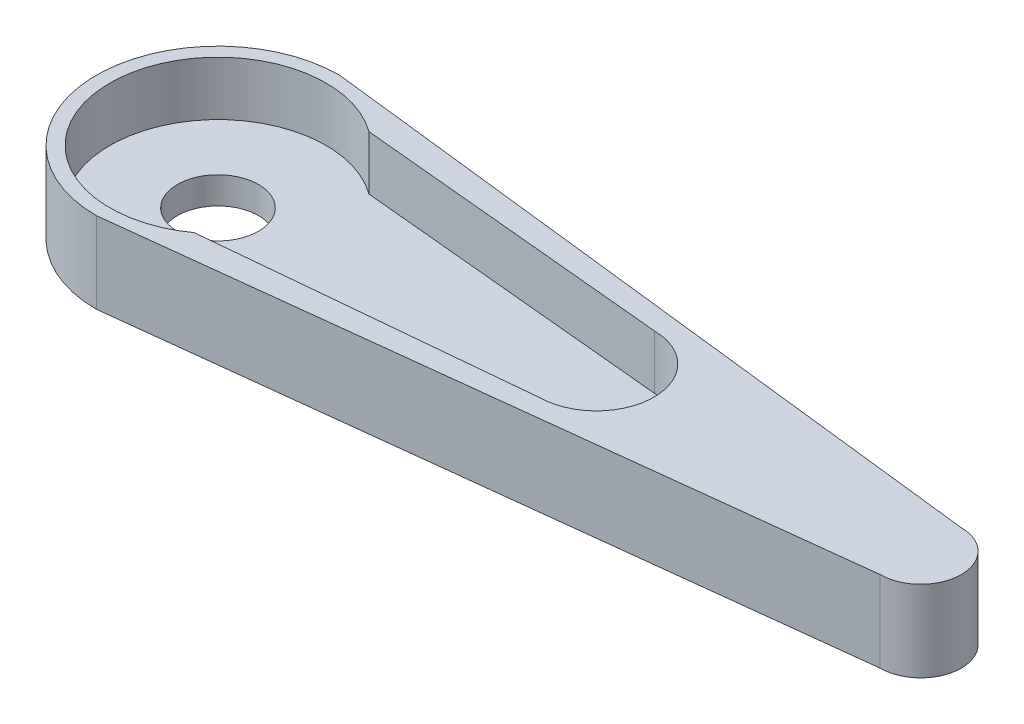
SolidWorks part; units mm, degrees
ref_plane "Front Plane" through (0, 0, 0) normal (0, 0, 1) x (1, 0, 0)
ref_plane "Top Plane" through (0, 0, 0) normal (0, 1, 0) x (1, 0, 0)
ref_plane "Right Plane" through (0, 0, 0) normal (1, 0, 0) x (0, 0, -1)
sketch "Sketch2" plane through (0, 0, 0) normal (0, 1, 0) x (1, 0, 0)
  line L0 (-24.822, 2.75) -> (-24.822, -2.75) construction
  line L1 (-26.9871, 0) -> (-12.9871, 0) construction
  line L4 (-26.9871, 4.5) -> (-12.8647, 2.8705)
  line L5 (-0.9871, -1.5) -> (-26.9871, -4.5)
  line L6 (-26.9871, 0) -> (-1.9871, 0) construction
  line L7 (-26.9871, -4.5) -> (-0.1594, -1.4045) construction
  line L8 (-26.9871, 4.5) -> (-0.9871, 1.5) construction
  line L10 (-12.8647, 2.8705) -> (-0.9871, 1.5)
  line L11 (-24.775, 3.2478) -> (-12.94, 2.1284)
  line L12 (-12.94, -2.1284) -> (-24.775, -3.2478)
  circle A1 centre (-26.9871, 0) radius 1.5
  circle A3 centre (-26.9871, 0) radius 4.5
  circle A4 centre (-12.9871, 0) radius 2.6306
  circle A5 centre (-0.9871, 0) radius 1.5
  circle A6 centre (-12.9871, 0) radius 2.1306
  circle A7 centre (-26.9871, 0) radius 4
  point P1 (-26.9871, 4.5)
  point P5 (-26.9871, -4.5)
  point P8 (-0.9871, -2.9961)
  point P9 (0, 0)
  point P27 (-0.9871, -1.5)
  dimension "D1" = 5.5
  dimension "D3" = 14
  dimension "D7" = 3
  dimension "D6" = 26
extrude "Boss-Extrude1" add sketch "Sketch2" along normal blind 1 contours A7 A1 | A7 L12 A3 L11 | A4 L11 A3 L12 | A6 L11 A4 L12 | A6 region at (-22.8851, 0, -1.6776) region at (-19.2242, 0, 0) region at (-23.5233, 0, -1.7634) region at (-13.6525, 0, -2.1431) region at (-12.9871, 0, 0)
extrude "Boss-Extrude2" add sketch "Sketch2<3>" along normal blind 3 contours A5 L10 L4 A3 L11 A4 L12 L5 | A6 L12 A4 L11 | A7 L11 A3 L4 L5 L12 | A5 region at (-26.4883, 0, -4.3231) region at (-19.4439, 0, -3.3632) region at (-0.9871, 0, 0) region at (-11.7199, 0, -2.2297)
sketch "Sketch2<3>" plane through (0, 0, 0) normal (0, 1, 0) x (1, 0, 0) same geometry as "Sketch2"
